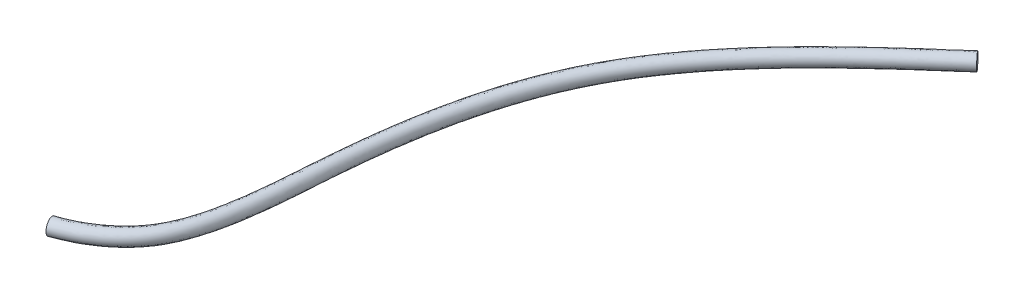
SolidWorks part; units mm, degrees
ref_plane "Front Plane" through (0, 0, 0) normal (0, 0, 1) x (1, 0, 0)
ref_plane "Top Plane" through (0, 0, 0) normal (0, 1, 0) x (1, 0, 0)
ref_plane "Right Plane" through (0, 0, 0) normal (1, 0, 0) x (0, 0, -1)
sketch "Sketch1" plane through (0, 0, 0) normal (0, 1, 0) x (1, 0, 0)
  spline S0 degree 3 poles (0, 0) (7.4762, 2.5197) (20.4493, 10.93) (28.1703, 36.1622) (29.6738, 77.2962) (41.4117, 145.1166) (85.0633, 183.6117) (107.6672, 203.3919) knots 0 0 0 0 0.100397 0.177006 0.31773 0.618652 1 1 1 1
  dimension "D1" = 203.3919
sweep "Sweep1" add path "Sketch1" circular profile diameter 5.08 parameters "D3"=5.08
